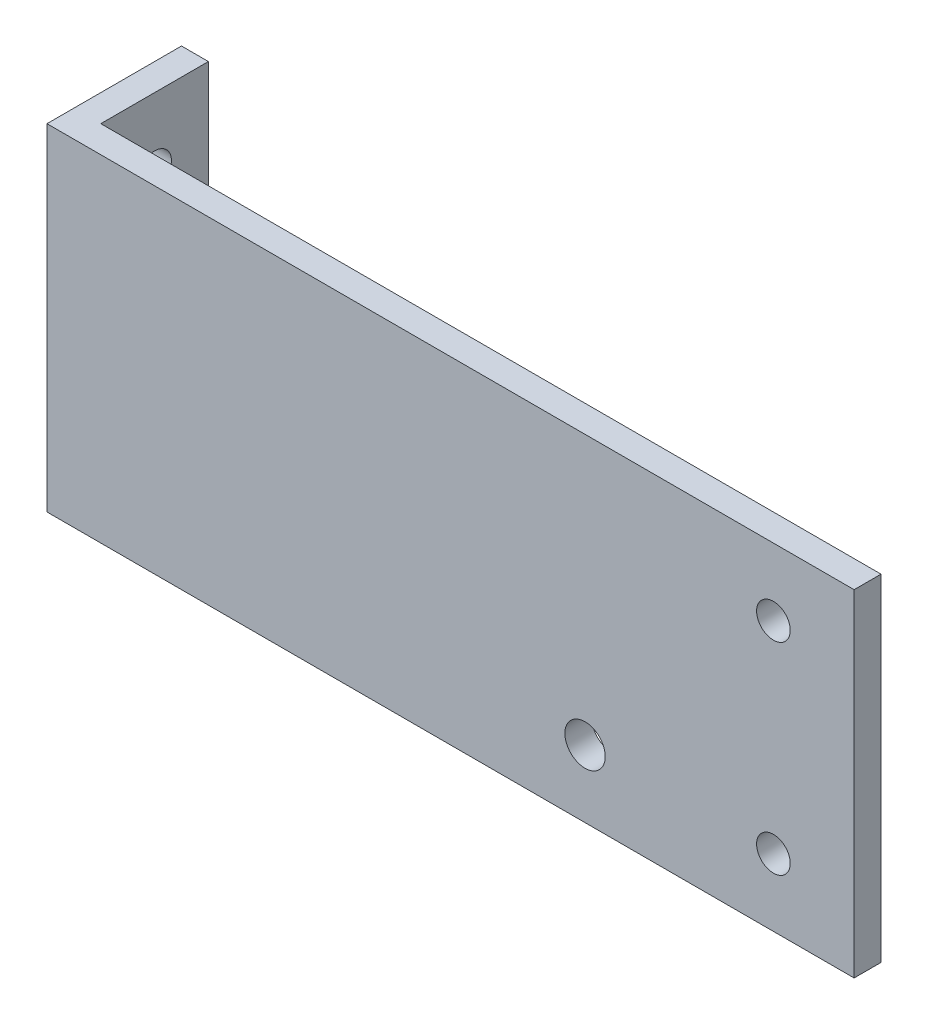
SolidWorks part; units mm, degrees
ref_plane "Спереди" through (0, 0, 0) normal (0, 0, 1) x (1, 0, 0)
ref_plane "Сверху" through (0, 0, 0) normal (0, 1, 0) x (1, 0, 0)
ref_plane "Справа" through (0, 0, 0) normal (1, 0, 0) x (0, 0, -1)
sketch "Эскиз1" plane through (0, 0, 0) normal (0, 1, 0) x (1, 0, 0)
  line L1 (0, 0) -> (120, 0)
  line L2 (0, 0) -> (0, 4)
  line L3 (4, 4) -> (120, 4)
  line L4 (120, 0) -> (120, 4)
  line L6 (0, 4) -> (0, 20)
  line L7 (0, 20) -> (4, 20)
  line L8 (4, 4) -> (4, 20)
  dimension "D1" = 120
  dimension "D2" = 4
  dimension "D3" = 20
  dimension "D4" = 4
extrude "Бобышка-Вытянуть1" add sketch "Эскиз1" along normal blind 50
sketch "Эскиз2" plane through (0, 0, 0) normal (-1, 0, 0) x (0, 0, 1)
  line L0 (-12, 44.9311) -> (-12, 11.555) construction
  line L2 (-20, 0) -> (0, 0) construction
  line L3 (0, 50) -> (0, 0) construction
  circle A0 centre (-12, 40) radius 2.5
  circle A1 centre (-12, 10) radius 2.5
  dimension "D2" = 5
  dimension "D3" = 5
  dimension "D1" = 12
  dimension "D4" = 30
  dimension "D5" = 10
extrude "Вырез-Вытянуть1" cut sketch "Эскиз2" against normal blind 10
sketch "Эскиз3" plane through (0, 0, 0) normal (0, 0, 1) x (1, 0, 0)
  line L0 (108, 46.6766) -> (108, 6.7064) construction
  line L1 (120, 50) -> (120, 0) construction
  line L2 (0, 0) -> (120, 0) construction
  line L4 (0, 50) -> (0, 0) construction
  circle A0 centre (108, 40) radius 2.5
  circle A1 centre (108, 10) radius 2.5
  circle A2 centre (80, 10) radius 3
  dimension "D2" = 5
  dimension "D3" = 5
  dimension "D6" = 6
  dimension "D1" = 12
  dimension "D4" = 30
  dimension "D5" = 10
  dimension "D7" = 10
  dimension "D8" = 80
extrude "Вырез-Вытянуть2" cut sketch "Эскиз3" against normal blind 10
